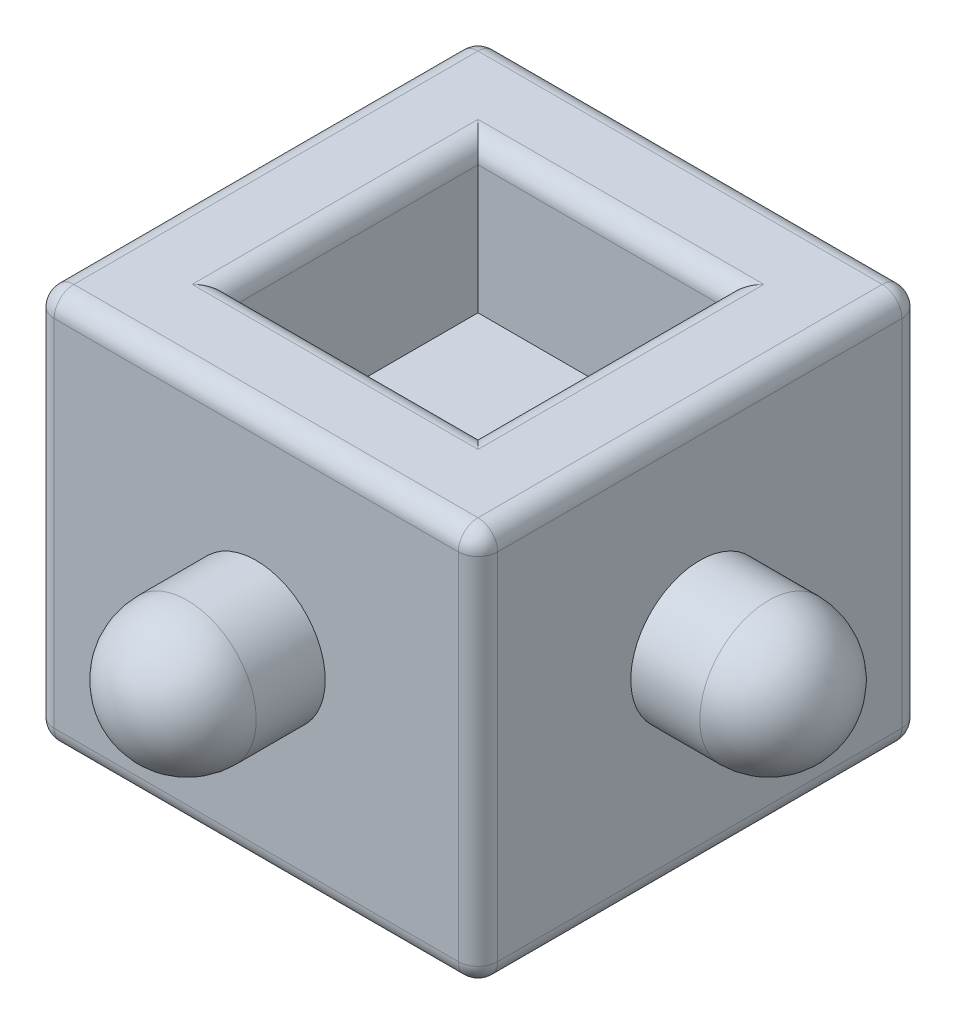
SolidWorks part; units mm, degrees
ref_plane "前视基准面" through (0, 0, 0) normal (0, 0, 1) x (1, 0, 0)
ref_plane "上视基准面" through (0, 0, 0) normal (0, 1, 0) x (1, 0, 0)
ref_plane "右视基准面" through (0, 0, 0) normal (1, 0, 0) x (0, 0, -1)
sketch "草图1" plane through (0, 0, 0) normal (0, 1, 0) x (1, 0, 0)
  line L0 (2.25, 2.25) -> (2.25, -2.25)
  line L1 (2.25, 2.25) -> (-2.25, 2.25)
  line L2 (2.25, -2.25) -> (-2.25, -2.25)
  line L3 (-2.25, 2.25) -> (-2.25, -2.25)
  line L4 (2.25, 2.25) -> (-2.25, -2.25) construction
  line L5 (2.25, -2.25) -> (-2.25, 2.25) construction
  point P1 (0, 0)
  dimension "D1" = 4.5
  dimension "D2" = 4.5
extrude "凸台-拉伸1" add sketch "草图1" along normal blind 2 and the other way blind 2
sketch "草图2" plane through (0, 2, 0) normal (0, 1, 0) x (1, 0, 0)
  line L0 (1.25, 1.25) -> (1.25, -1.25)
  line L1 (1.25, 1.25) -> (-1.25, 1.25)
  line L2 (1.25, -1.25) -> (-1.25, -1.25)
  line L3 (-1.25, 1.25) -> (-1.25, -1.25)
  line L4 (1.25, 1.25) -> (-1.25, -1.25) construction
  line L5 (1.25, -1.25) -> (-1.25, 1.25) construction
  point P1 (0, 0)
  dimension "D1" = 2.5
  dimension "D2" = 2.5
extrude "切除-拉伸1" cut sketch "草图2" against normal blind 1.5
mirror "镜向1" about plane through (0, 0, 0) normal (0, 1, 0) of "切除-拉伸1"
sketch "草图3" plane through (0, 0, 0) normal (0, 1, 0) x (1, 0, 0)
  line L0 (0, 2.25) -> (-0.7, 2.25)
  line L1 (2.25, 2.25) -> (-2.25, 2.25) construction
  line L2 (-0.7, 2.25) -> (-0.7, 2.95)
  line L3 (0, 2.25) -> (0, 2.95)
  line L4 (0, 2.95) -> (0, 3.65)
  arc A0 (0, 3.65) -> (-0.7, 2.95) centre (0, 2.95) ccw
  dimension "D1" = 0.7
  dimension "D2" = 0.7
  dimension "D3" = 0.7
revolve "旋转1" add sketch "草图3" angle 360 about L4
mirror "镜向2" about plane through (0, 0, 0) normal (0, 0, 1) of "旋转1"
sketch "草图5" plane through (0, 0, 0) normal (0, 1, 0) x (1, 0, 0)
  line L0 (-2.25, 0) -> (-2.95, 0)
  line L1 (-2.25, 2.25) -> (-2.25, -2.25) construction
  line L2 (-2.25, 0) -> (-2.25, 0.7)
  line L3 (-2.25, 0.7) -> (-2.95, 0.7)
  line L4 (-2.95, 0) -> (-3.65, 0)
  arc A0 (-2.95, 0.7) -> (-3.65, 0) centre (-2.95, 0) ccw
  dimension "D1" = 0.7
  dimension "D2" = 0.7
  dimension "D3" = 0.7
revolve "旋转2" add sketch "草图5" angle 360 about L0
mirror "镜向3" about plane through (0, 0, 0) normal (1, 0, 0) of "旋转2"
fillet "圆角1" radius 0.2 20 edges at (1.25, -2, 0) (0, -2, 1.25) (-1.25, -2, 0) (0, -2, -1.25) (-2.25, -2, 0) (0, -2, 2.25) (2.25, -2, 0) (0, -2, -2.25) (2.25, 2, 0) (0, 2, 2.25) (-2.25, 2, 0) (0, 2, -2.25) (-1.25, 2, 0) (0, 2, 1.25) (1.25, 2, 0) (0, 2, -1.25) (-2.25, 0, 2.25) (2.25, 0, 2.25) (-2.25, 0, -2.25) (2.25, 0, -2.25)
